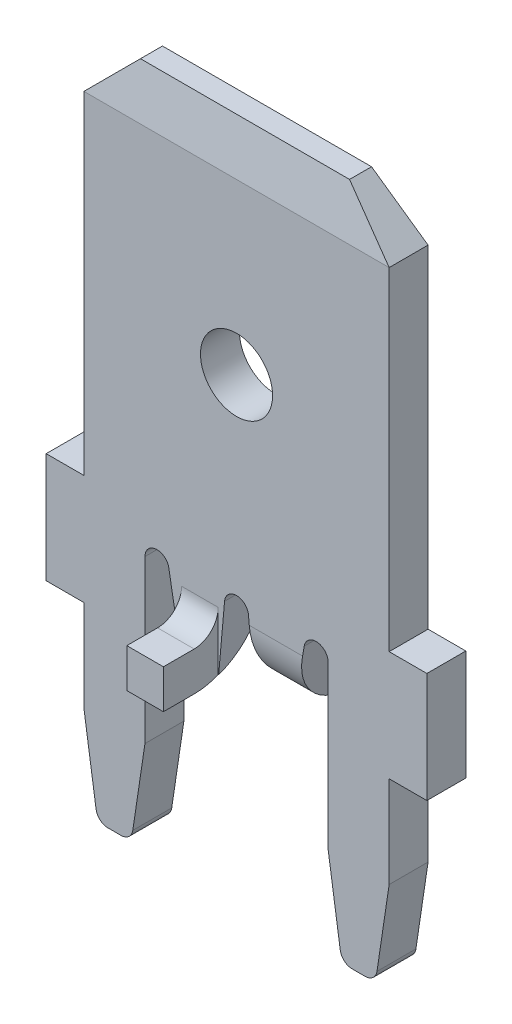
SolidWorks part; units mm, degrees
material "Brass"
ref_plane "Plane1" through (0, 0, 0) normal (0, 0, 1) x (1, 0, 0)
ref_plane "Plane2" through (0, 0, 0) normal (0, 1, 0) x (1, 0, 0)
ref_plane "Plane3" through (0, 0, 0) normal (1, 0, 0) x (0, 0, -1)
sketch "Sketch1" plane through (0, 0, 0) normal (0, 0, 1) x (1, 0, 0)
  line L0 (0, 4.52) -> (0, 0) construction
  line L1 (-3.175, 4.52) -> (3.175, 4.52)
  line L2 (-3.175, 4.52) -> (-3.175, -3.4)
  line L3 (-3.175, -3.4) -> (3.175, -3.4) construction
  line L4 (3.175, 4.52) -> (3.175, -3.4)
  line L5 (3.175, -3.4) -> (3.96, -3.4)
  line L6 (3.96, -3.4) -> (3.96, -5.69)
  line L7 (3.96, -5.69) -> (3.175, -5.69)
  line L8 (3.175, -5.69) -> (3.175, -7.595)
  line L9 (3.175, -7.595) -> (2.9219, -9.287)
  line L10 (2.6746, -9.5) -> (2.4054, -9.5)
  line L11 (2.54, -9.5) -> (2.54, -5.9053) construction
  line L12 (1.905, -7.595) -> (2.1581, -9.287)
  line L13 (1.905, -4.226) -> (1.905, -7.595)
  line L14 (1.905, -5.69) -> (-1.948, -5.69) construction
  line L15 (0.381, -5.69) -> (0.249, -4.2039)
  line L16 (0, 0) -> (0, -6.4344) construction
  line L17 (-0.381, -5.69) -> (-0.249, -4.2039)
  line L18 (0.381, -5.69) -> (1.143, -5.69)
  line L19 (0.381, -5.69) -> (0.381, -4.88) construction
  line L20 (0.381, -4.88) -> (1.143, -4.88) construction
  line L21 (1.143, -5.69) -> (1.143, -4.88) construction
  line L22 (-1.905, -7.595) -> (-2.1581, -9.287)
  line L23 (-2.6746, -9.5) -> (-2.4054, -9.5)
  line L24 (-3.175, -7.595) -> (-2.9219, -9.287)
  line L25 (-3.175, -5.69) -> (-3.175, -7.595)
  line L26 (-3.96, -5.69) -> (-3.175, -5.69)
  line L27 (-3.96, -3.4) -> (-3.96, -5.69)
  line L28 (-3.175, -3.4) -> (-3.96, -3.4)
  line L29 (1.143, -5.69) -> (1.4088, -4.1826)
  line L30 (-0.381, -5.69) -> (-1.143, -5.69)
  line L31 (-1.143, -5.69) -> (-1.4088, -4.1826)
  line L32 (-1.905, -4.226) -> (-1.905, -7.595)
  line L33 (-1.655, -4.226) -> (1.655, -4.226) construction
  circle A0 centre (0, 0) radius 0.75
  arc A1 (2.9219, -9.287) -> (2.6746, -9.5) centre (2.6746, -9.25) cw
  arc A2 (2.4054, -9.5) -> (2.1581, -9.287) centre (2.4054, -9.25) cw
  arc A3 (-2.4054, -9.5) -> (-2.1581, -9.287) centre (-2.4054, -9.25) ccw
  arc A4 (-2.9219, -9.287) -> (-2.6746, -9.5) centre (-2.6746, -9.25) ccw
  arc A5 (1.905, -4.226) -> (1.4088, -4.1826) centre (1.655, -4.226) ccw
  arc A6 (-1.905, -4.226) -> (-1.4088, -4.1826) centre (-1.655, -4.226) cw
  arc A7 (0.249, -4.2039) -> (-0.249, -4.2039) centre (0, -4.226) ccw
  point P20 (2.89, -9.5)
  point P23 (2.19, -9.5)
  point P52 (0, -1.3999)
  dimension "D4" = 1.5
  dimension "D12" = 0.25
  dimension "D13" = 0.381
  dimension "D17" = 0.25
  dimension "D19" = 0.25
  dimension "D1" = 3.4
  dimension "D2" = 7.92
  dimension "D3" = 6.35
  dimension "D5" = 3.96
  dimension "D6" = 14.02
  dimension "D7" = 3.81
  dimension "D8" = 2.54
  dimension "D9" = 1.905
  dimension "D10" = 1.27
  dimension "D11" = 0.7
  dimension "D14" = 0.762
  dimension "D15" = 5.075
  dimension "D16" = 10
  dimension "D18" = 0.81
extrude "Extrude1" add sketch "Sketch1" along normal blind 0.81
chamfer "Chamfer4" distance 1 angle 10 1 edges at (0, 4.52, 0.81) first distance on face at (0, -5.6354, 0.81)
chamfer "Chamfer5" distance 1 angle 10 1 edges at (0, 4.52, 0) first distance on face at (0, -5.6354, 0)
chamfer "Chamfer1" distance 1 angle 45 2 edges at (-3.175, 4.52, 0.405) (3.175, 4.52, 0.405)
sketch "Sketch2" plane through (0, 0, 0.81) normal (0, 0, 1) x (1, 0, 0)
  line L1 (-1.143, -5.69) -> (-0.381, -5.69)
  line L2 (-1.143, -5.69) -> (-1.143, -4.88)
  line L3 (-1.143, -4.88) -> (-0.381, -4.88)
  line L4 (-0.381, -5.69) -> (-0.381, -4.88)
  dimension "D1" = 0.81
extrude "Extrude2" add sketch "Sketch2" along normal blind 1.14
sketch "Sketch3" plane through (0, 0, 0) normal (0, 0, -1) x (-1, 0, 0)
  line L1 (-0.381, -5.69) -> (-1.143, -5.69)
  line L2 (-0.381, -5.69) -> (-0.381, -4.88)
  line L3 (-0.381, -4.88) -> (-1.143, -4.88)
  line L4 (-1.143, -5.69) -> (-1.143, -4.88)
  dimension "D1" = 0.81
extrude "Extrude3" add sketch "Sketch3" along normal blind 1.14
fillet "Fillet1" radius 0.5 2 edges at (0.762, -4.88, 0) (-0.762, -4.88, 0.81)
fillet "Fillet2" radius 1.31 2 edges at (-0.762, -5.69, 0) (0.762, -5.69, 0.81)
ref_plane "Plane4" through (-2.54, 0, 0) normal (1, 0, 0) x (0, 0, -1)
ref_plane "Plane5" through (0, 0, 0.405) normal (0, 0, 1) x (1, 0, 0)
ref_axis "Axis1" through (-2.54, -50, 0.405) along (0, 1, 0)
ref_axis "Axis2" through (0, 50, 0) along (0, -1, 0)
